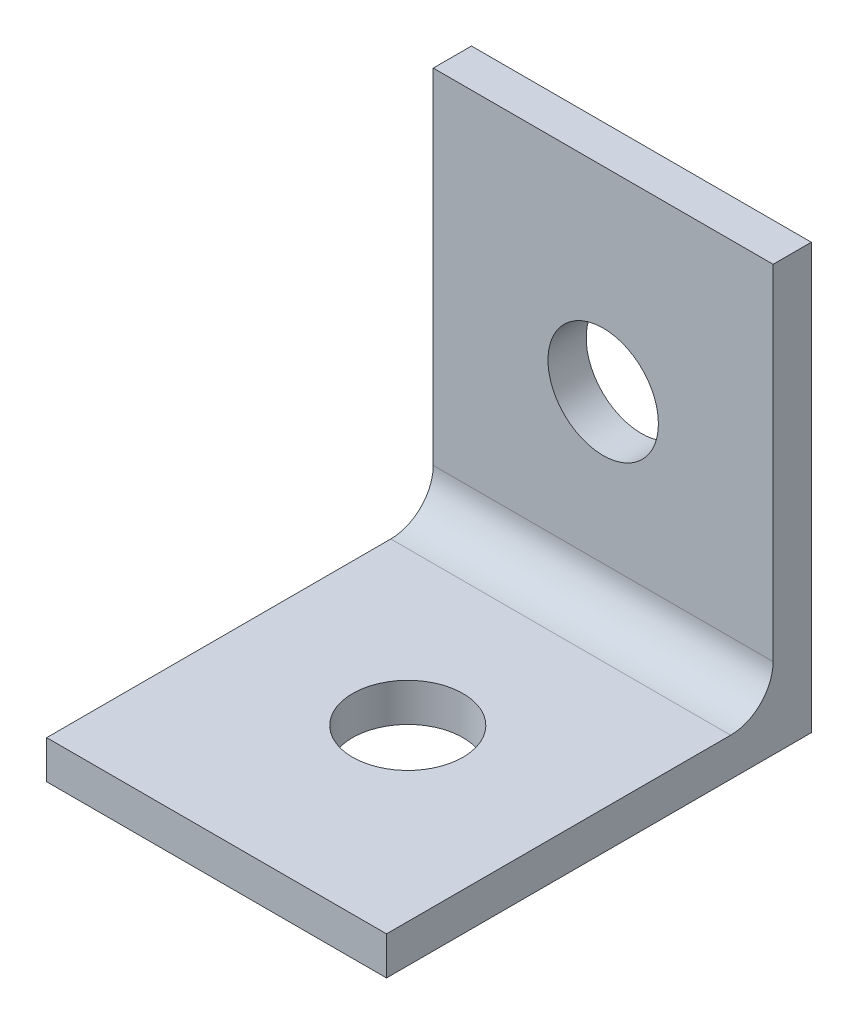
SolidWorks part; units mm, degrees
ref_plane "Front Plane" through (0, 0, 0) normal (0, 0, 1) x (1, 0, 0)
ref_plane "Top Plane" through (0, 0, 0) normal (0, 1, 0) x (1, 0, 0)
ref_plane "Right Plane" through (0, 0, 0) normal (1, 0, 0) x (0, 0, -1)
sketch "Sketch1" plane through (0, 0, 0) normal (0, 0, 1) x (1, 0, 0)
  line L1 (0, 0) -> (16, 0)
  line L2 (0, 0) -> (0, 20)
  line L3 (0, 20) -> (16, 20)
  line L4 (16, 0) -> (16, 20)
  dimension "D1" = 16
  dimension "D2" = 20
extrude "Boss-Extrude1" add sketch "Sketch1" along normal blind 1.8
sketch "Sketch2" plane through (0, 0, 0) normal (0, -1, 0) x (1, 0, 0)
  line L1 (0, 1.8) -> (16, 1.8)
  line L2 (0, 1.8) -> (0, 20)
  line L3 (0, 20) -> (16, 20)
  line L4 (16, 1.8) -> (16, 20)
  dimension "D1" = 18.2
  dimension "D2" = 16
extrude "Boss-Extrude2" add sketch "Sketch2" against normal blind 1.8
sketch "Sketch3" plane through (0, 0, 1.8) normal (0, 0, 1) x (1, 0, 0)
  line L0 (16, 1.8) -> (16, 20) construction
  line L1 (0, 1.8) -> (16, 1.8) construction
  circle A0 centre (8, 10.8) radius 2.6
  dimension "D1" = 5.2
  dimension "D2" = 8
  dimension "D3" = 9
extrude "Cut-Extrude1" cut sketch "Sketch3" against normal blind 1.8
sketch "Sketch4" plane through (0, 1.8, 0) normal (0, 1, 0) x (1, 0, 0)
  line L0 (16, -1.8) -> (16, -20) construction
  line L1 (16, 0) -> (0, 0) construction
  circle A0 centre (8, -11) radius 2.6
  dimension "D1" = 8
  dimension "D2" = 5.2
  dimension "D3" = 11
extrude "Cut-Extrude2" cut sketch "Sketch4" against normal blind 1.8
fillet "Fillet1" radius 2 1 edges at (8, 1.8, 1.8)
